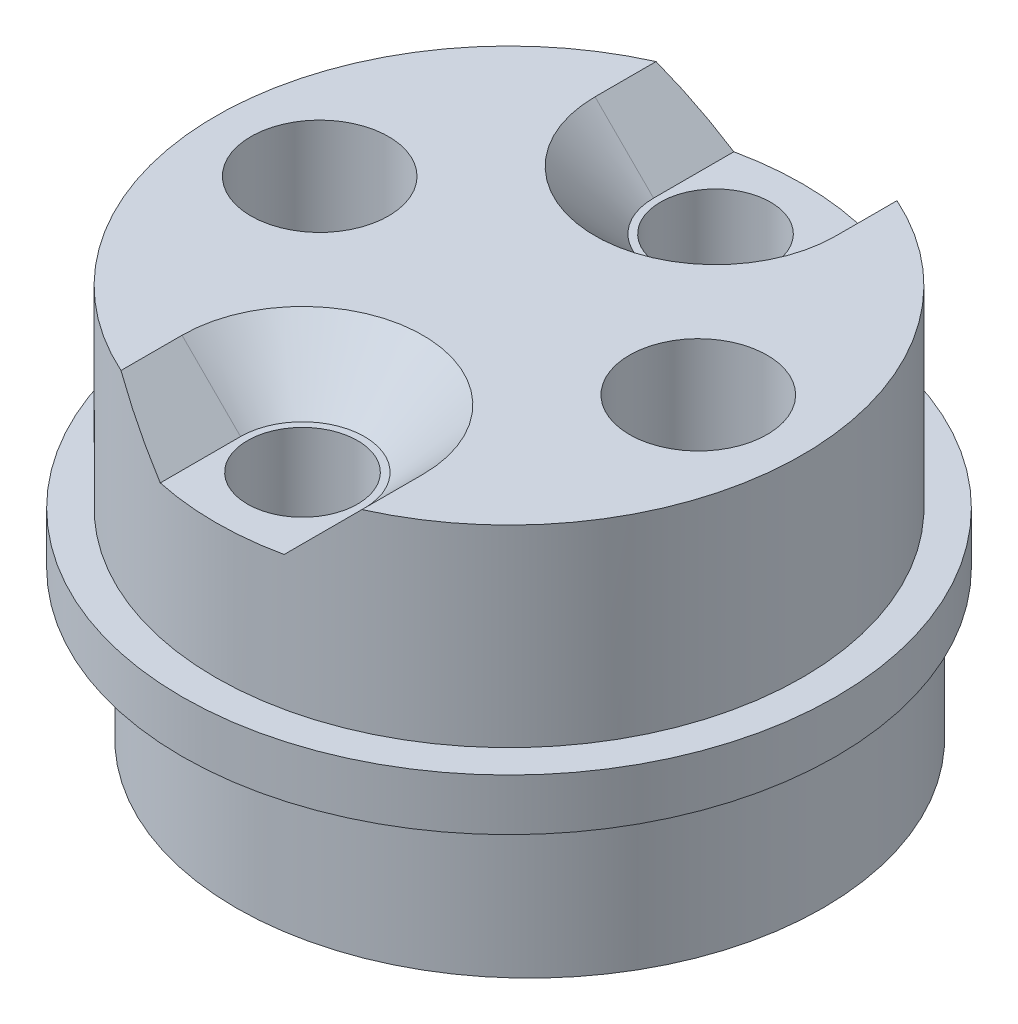
SolidWorks part; units mm, degrees
material "Like ABS"
ref_plane "Front Plane" through (0, 0, 0) normal (0, 0, 1) x (1, 0, 0)
ref_plane "Top Plane" through (0, 0, 0) normal (0, 1, 0) x (1, 0, 0)
ref_plane "Right Plane" through (0, 0, 0) normal (1, 0, 0) x (0, 0, -1)
sketch "Sketch1" plane through (0, 0, 0) normal (0, 1, 0) x (1, 0, 0)
  circle A0 centre (0, 0) radius 8.525
  dimension "D1" = 17.05
extrude "Boss-Extrude11" add sketch "Sketch1" along normal blind 4
sketch "Sketch20" plane through (0, 4, 0) normal (0, 1, 0) x (1, 0, 0)
  line L0 (0, 0) -> (1.2, 0) construction
  circle A0 centre (1.2, 0) radius 8.525
  dimension "D2" = 17.05
  dimension "D1" = 1.2
extrude "Boss-Extrude12" add sketch "Sketch20" along normal blind 4
sketch "Sketch21" plane through (0, 8, 0) normal (0, 1, 0) x (1, 0, 0)
  line L0 (0, 0) -> (0.6, 0) construction
  circle A0 centre (0.6, 0) radius 9.5
  dimension "D2" = 19
  dimension "D1" = 0.6
extrude "Boss-Extrude13" add sketch "Sketch21" along normal blind 1.5
sketch "Sketch22" plane through (0, 9.5, 0) normal (0, 1, 0) x (1, 0, 0)
  line L0 (0, 0) -> (0.6, 0) construction
  circle A0 centre (0.6, 0) radius 8.525
  dimension "D2" = 17.05
  dimension "D1" = 0.6
extrude "Boss-Extrude14" add sketch "Sketch22" along normal blind 5.6
sketch "Sketch30" plane through (0, 0, 0) normal (0, -1, 0) x (1, 0, 0)
  line L0 (0, 0) -> (0.6, 0) construction
  circle A1 centre (0.6, 0) radius 8.525
  dimension "D1" = 0.6
  dimension "D2" = 17.05
extrude "Boss-Extrude15" add sketch "Sketch30" along normal blind 14.75
sketch "Sketch33" plane through (0, -14.75, 0) normal (0, -1, 0) x (1, 0, 0)
  line L0 (0, 0) -> (0.6, 0) construction
  circle A0 centre (0.6, 0) radius 2.1
  dimension "D2" = 4.2
  dimension "D1" = 0.6
extrude "Cut-Extrude14" cut sketch "Sketch33" against normal blind 5.8
sketch "Sketch35" plane through (0, 0, 0) normal (0, -1, 0) x (1, 0, 0)
  line L0 (0, 0) -> (0.6, 0) construction
  circle A0 centre (0.6, 0) radius 9.5
  dimension "D2" = 19
  dimension "D1" = 0.6
extrude "Boss-Extrude16" add sketch "Sketch35" along normal blind 1.25
sketch "Sketch36" plane through (0, -14.75, 0) normal (0, -1, 0) x (1, 0, 0)
  circle A0 centre (0.6, 0) radius 6 construction
  circle A1 centre (0.6, 6) radius 1.6
  dimension "D1" = 12
  dimension "D2" = 3.2
extrude "Cut-Extrude15" cut sketch "Sketch36" against normal up to surface (29.85 mm away) up to face at (0.6, 15.1, 8.525)
pattern_circular "CirPattern1" count 2 over 360 about axis through (0.6, -14.75, 0) along (0, 1, 0) of "Cut-Extrude15"
sketch "Sketch43" plane through (0, -14.75, 0) normal (0, -1, 0) x (1, 0, 0)
  circle A1 centre (-4.9, 0) radius 1.55
  circle A2 centre (6.1, 0) radius 1.55
  circle A3 centre (0.6, 0) radius 5.5 construction
  dimension "D1" = 11
  dimension "D2" = 3.1
extrude "Cut-Extrude20" cut sketch "Sketch43" against normal up to surface (29.85 mm away) up to face at (0.6, 15.1, -4.4)
sketch "Sketch44" plane through (0, 15.1, 0) normal (0, 1, 0) x (1, 0, 0)
  circle A0 centre (-4.9, 0) radius 2
  circle A1 centre (6.1, 0) radius 2
  dimension "D1" = 4
extrude "Cut-Extrude21" cut sketch "Sketch44" against normal blind 4
sketch "Sketch45" plane through (0, 15.1, 0) normal (0, 1, 0) x (1, 0, 0)
  line L2 (-2.9, -6) -> (-2.9, -10.8726)
  line L3 (-2.9, -10.8726) -> (4.1, -10.8726)
  line L4 (4.1, -6) -> (4.1, -10.8726)
  line L6 (-2.9, 6) -> (-2.9, 11.4221)
  line L7 (-2.9, 11.4221) -> (4.1, 11.4221)
  line L8 (4.1, 6) -> (4.1, 11.4221)
  arc A0 (-2.9, 6) -> (4.1, 6) centre (0.6, 6) ccw
  arc A1 (4.1, -6) -> (-2.9, -6) centre (0.6, -6) ccw
  dimension "D1" = 7
  dimension "D2" = 7
extrude "Cut-Extrude22" cut sketch "Sketch45" against normal blind 1.7
sketch "Sketch46" plane through (0, -14.75, 0) normal (0, -1, 0) x (1, 0, 0)
  line L1 (-4.9, 3) -> (-9.7199, 3)
  line L3 (-4.9, -3) -> (-9.7199, -3)
  line L4 (-9.7199, 3) -> (-9.7199, -3)
  line L5 (6.1, 3) -> (10.8894, 3)
  line L7 (6.1, -3) -> (10.8894, -3)
  line L8 (10.8894, 3) -> (10.8894, -3)
  arc A0 (-4.9, -3) -> (-4.9, 3) centre (-4.9, 0) ccw
  arc A1 (6.1, 3) -> (6.1, -3) centre (6.1, 0) ccw
  dimension "D1" = 6
extrude "Cut-Extrude23" cut sketch "Sketch46" against normal blind 3
sketch "Sketch47" plane through (0, -14.75, 0) normal (0, -1, 0) x (1, 0, 0)
  line L1 (-13.4236, 13.1214) -> (15.4466, 13.1214)
  line L2 (-13.4236, 13.1214) -> (-13.4236, -12.7099)
  line L3 (-13.4236, -12.7099) -> (15.4466, -12.7099)
  line L4 (15.4466, 13.1214) -> (15.4466, -12.7099)
extrude "Cut-Extrude24" cut sketch "Sketch47" against normal up to surface (18.75 mm away) up to face at (-7.925, 4, 0)
sketch "Sketch48" plane through (0, 4, 0) normal (0, -1, 0) x (1, 0, 0)
  line L1 (-1.8, 3) -> (4.2, 3)
  line L2 (-1.8, 3) -> (-1.8, -3)
  line L3 (-1.8, -3) -> (4.2, -3)
  line L4 (4.2, 3) -> (4.2, -3)
  circle A0 centre (1.2, 0) radius 3 construction
  dimension "D1" = 6
extrude "Boss-Extrude17" add sketch "Sketch48" along normal blind 3
fillet "Fillet1" radius 0.6 4 edges at (1.2, 1, 3) (4.2, 1, 0) (1.2, 1, -3) (-1.8, 1, 0)
chamfer "Chamfer1" distance 1.7 angle 45 6 edges at (4.1, 13.4, 6.8867) (-2.9, 13.4, 6.8867) (-2.9, 13.4, -6.8867) (4.1, 13.4, -6.8867) (0.6, 13.4, 2.5) (0.6, 13.4, -2.5)
